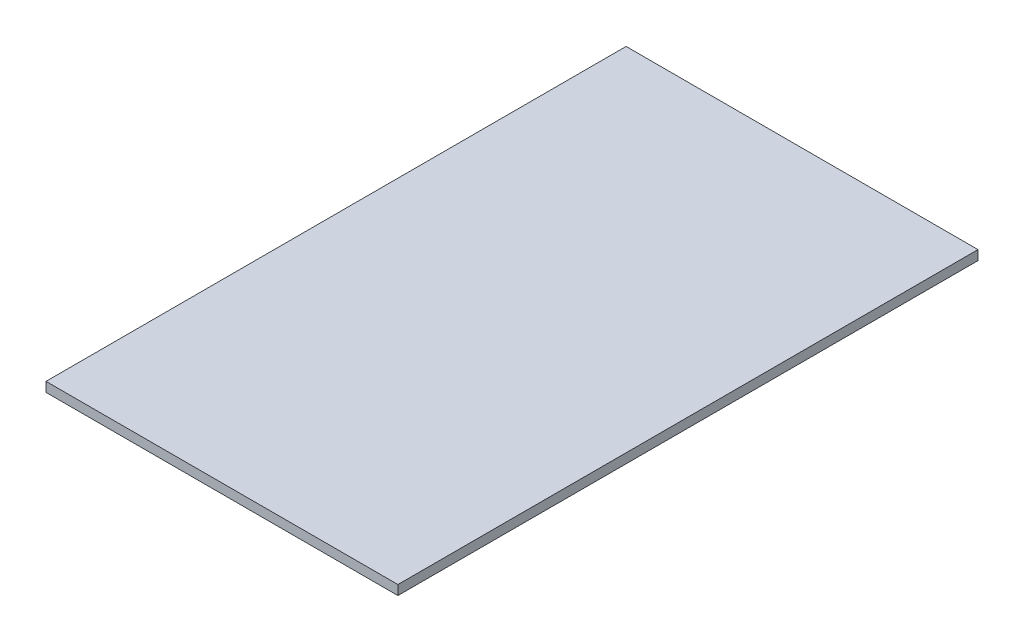
SolidWorks part; units mm, degrees
ref_plane "Front Plane" through (0, 0, 0) normal (0, 0, 1) x (1, 0, 0)
ref_plane "Top Plane" through (0, 0, 0) normal (0, 1, 0) x (1, 0, 0)
ref_plane "Right Plane" through (0, 0, 0) normal (1, 0, 0) x (0, 0, -1)
sketch "Sketch1" plane through (0, 0, 0) normal (0, 1, 0) x (1, 0, 0)
  line L1 (58.34, -96.1727) -> (-58.34, -96.1727)
  line L2 (58.34, -96.1727) -> (58.34, 96.1727)
  line L3 (58.34, 96.1727) -> (-58.34, 96.1727)
  line L4 (-58.34, -96.1727) -> (-58.34, 96.1727)
  line L5 (58.34, -96.1727) -> (-58.34, 96.1727) construction
  line L6 (58.34, 96.1727) -> (-58.34, -96.1727) construction
  point P0 (0, 0)
  dimension "D1" = 116.68
  dimension "D2" = 192.3454
extrude "Boss-Extrude1" add sketch "Sketch1" along normal blind 3.175
